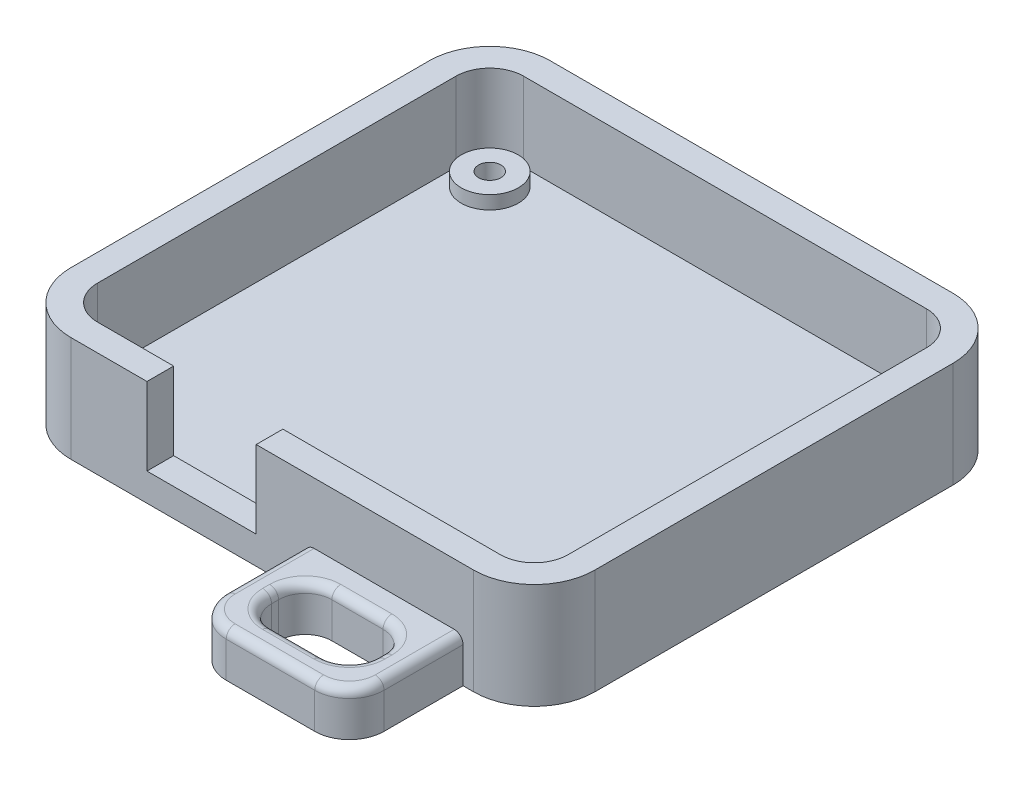
SolidWorks part; units mm, degrees
ref_plane "Front Plane" through (0, 0, 0) normal (0, 0, 1) x (1, 0, 0)
ref_plane "Top Plane" through (0, 0, 0) normal (0, 1, 0) x (1, 0, 0)
ref_plane "Right Plane" through (0, 0, 0) normal (1, 0, 0) x (0, 0, -1)
sketch "Sketch1" plane through (0, 0, 0) normal (0, 1, 0) x (1, 0, 0)
  line L0 (3.81, 3) -> (49.09, 3)
  line L1 (3.81, 0) -> (49.09, 0)
  line L2 (0, -3.81) -> (0, -44.09)
  line L3 (3.81, -47.9) -> (49.09, -47.9)
  line L4 (52.9, -3.81) -> (52.9, -44.09)
  line L5 (55.9, -3.81) -> (55.9, -44.09)
  line L6 (3.81, -50.9) -> (49.09, -50.9)
  line L7 (-3, -3.81) -> (-3, -44.09)
  arc A0 (52.9, -3.81) -> (49.09, 0) centre (49.09, -3.81) ccw
  arc A1 (0, -3.81) -> (3.81, 0) centre (3.81, -3.81) cw
  arc A2 (3.81, -47.9) -> (0, -44.09) centre (3.81, -44.09) cw
  arc A3 (52.9, -44.09) -> (49.09, -47.9) centre (49.09, -44.09) cw
  circle A4 centre (49.09, -44.09) radius 1.25
  circle A5 centre (3.81, -44.09) radius 1.25
  circle A6 centre (3.81, -3.81) radius 1.25
  circle A7 centre (49.09, -3.81) radius 1.25
  arc A8 (55.9, -3.81) -> (49.09, 3) centre (49.09, -3.81) ccw
  arc A9 (55.9, -44.09) -> (49.09, -50.9) centre (49.09, -44.09) cw
  arc A10 (3.81, -50.9) -> (-3, -44.09) centre (3.81, -44.09) cw
  arc A11 (-3, -3.81) -> (3.81, 3) centre (3.81, -3.81) cw
  circle A12 centre (3.81, -3.81) radius 3.21
  circle A13 centre (49.09, -3.81) radius 3.21
  circle A14 centre (49.09, -44.09) radius 3.21
  circle A15 centre (3.81, -44.09) radius 3.21
  point P7 (52.9, 0)
  point P10 (0, 0)
  point P15 (52.9, -47.9)
  dimension "D3" = 3.81
  dimension "D4" = 3.81
  dimension "D5" = 3.81
  dimension "D6" = 3.81
  dimension "D7" = 3
  dimension "D8" = 2.5
  dimension "D9" = 2.5
  dimension "D10" = 2.5
  dimension "D11" = 2.5
  dimension "D12" = 6.42
  dimension "D13" = 6.42
  dimension "D14" = 6.42
  dimension "D15" = 6.42
  dimension "D1" = 52.9
  dimension "D2" = 47.9
extrude "Boss-Extrude1" add sketch "Sketch1" against normal blind 3 contours L7 A10 L6 A9 L5 A8 L0 A11
extrude "Cut-Extrude1" cut sketch "Sketch1<3>" against normal up to next contours A6 | A5 | A4 | A7 region at (49.09, 0, 44.09) region at (3.81, 0, 44.09) region at (3.81, 0, 3.81) region at (49.09, 0, 3.81)
sketch "Sketch1<3>" plane through (0, 0, 0) normal (0, 1, 0) x (1, 0, 0) same geometry as "Sketch1"
extrude "Boss-Extrude2" add sketch "Sketch1<4>" along normal blind 8.86 contours A11 L7 A10 L6 A9 L5 A8 L0 L4 A3 L3 A2 L2 A1 L1 A0 region at (26.45, 0, -2.2016)
sketch "Sketch1<4>" plane through (0, 0, 0) normal (0, 1, 0) x (1, 0, 0) same geometry as "Sketch1"
extrude "Boss-Extrude3" add sketch "Sketch1<5>" along normal blind 1.5 contours A13 A7 | A14 A4 | A15 A5 | A12 A6 region at (0.6908, 0, 3.81) region at (45.9708, 0, 3.81) region at (45.9708, 0, 44.09) region at (0.6908, 0, 44.09)
sketch "Sketch1<5>" plane through (0, 0, 0) normal (0, 1, 0) x (1, 0, 0) same geometry as "Sketch1"
sketch "Sketch2" plane through (0, 0, 50.9) normal (0, 0, 1) x (1, 0, 0)
  line L0 (3.81, -3) -> (49.09, -3) construction
  line L1 (12.36, 8.865) -> (24.64, 8.865)
  line L2 (12.36, 8.865) -> (12.36, 0.135)
  line L3 (12.36, 0.135) -> (24.64, 0.135)
  line L4 (24.64, 8.865) -> (24.64, 0.135)
  line L5 (-3, -3) -> (-3, 8.86) construction
  dimension "D1" = 3.135
  dimension "D2" = 8.73
  dimension "D3" = 12.28
  dimension "D4" = 15.36
extrude "Cut-Extrude2" cut sketch "Sketch2" against normal blind 3
sketch "Sketch8" plane through (0, -3, 0) normal (0, -1, 0) x (1, 0, 0)
  line L0 (3.81, 50.9) -> (49.09, 50.9) construction
  line L1 (47.9, 50.9) -> (30.15, 50.9)
  line L2 (47.9, 50.9) -> (47.9, 59.78)
  line L3 (44, 63.68) -> (34.05, 63.68)
  line L4 (30.15, 50.9) -> (30.15, 59.78)
  line L5 (55.9, 3.81) -> (55.9, 44.09) construction
  line L7 (41.9, 53.9) -> (36.15, 53.9)
  line L8 (44.9, 56.9) -> (44.9, 57.68)
  line L9 (41.9, 60.68) -> (36.15, 60.68)
  line L10 (33.15, 56.9) -> (33.15, 57.68)
  arc A0 (30.15, 59.78) -> (34.05, 63.68) centre (34.05, 59.78) cw
  arc A1 (47.9, 59.78) -> (44, 63.68) centre (44, 59.78) ccw
  arc A2 (33.15, 57.68) -> (36.15, 60.68) centre (36.15, 57.68) cw
  arc A3 (36.15, 53.9) -> (33.15, 56.9) centre (36.15, 56.9) cw
  arc A4 (44.9, 57.68) -> (41.9, 60.68) centre (41.9, 57.68) ccw
  arc A5 (41.9, 53.9) -> (44.9, 56.9) centre (41.9, 56.9) ccw
  point P10 (30.15, 63.68)
  point P13 (47.9, 63.68)
  point P20 (33.15, 60.68)
  point P23 (33.15, 53.9)
  point P26 (44.9, 60.68)
  dimension "D5" = 3.9
  dimension "D6" = 3.9
  dimension "D11" = 3
  dimension "D12" = 3
  dimension "D13" = 3
  dimension "D14" = 3
  dimension "D1" = 0
  dimension "D2" = 17.75
  dimension "D3" = 12.78
  dimension "D4" = 8
  dimension "D7" = 11.75
  dimension "D8" = 6.78
  dimension "D9" = 3
  dimension "D10" = 3
extrude "Boss-Extrude7" add sketch "Sketch8" against normal blind 5
fillet "Fillet4" radius 1 13 edges at (47.9, 2, 55.34) (46.7577, 2, 62.5377) (39.025, 2, 63.68) (31.2923, 2, 62.5377) (33.15, 2, 57.29) (34.0287, 2, 59.8013) (39.025, 2, 60.68) (44.0213, 2, 59.8013) (44.9, 2, 57.29) (44.0213, 2, 54.7787) (39.025, 2, 53.9) (30.15, 2, 55.34) (34.0287, 2, 54.7787)
